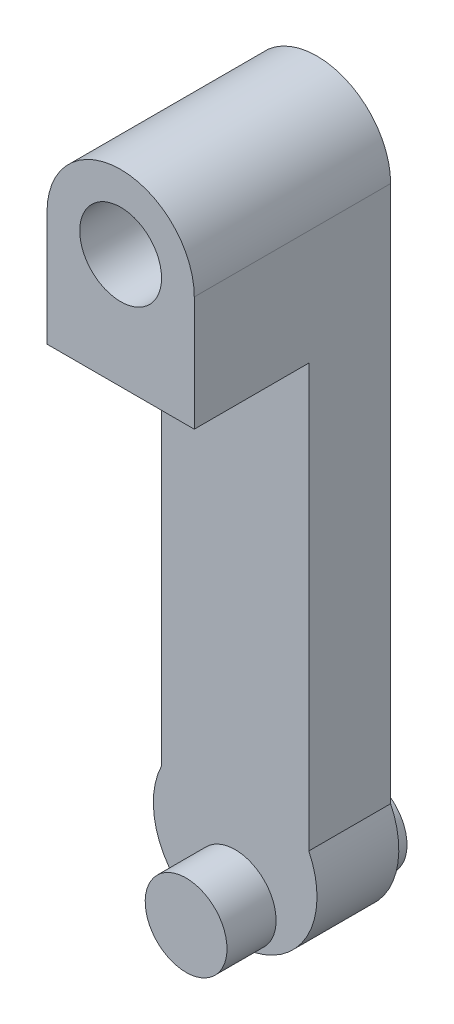
SolidWorks part; units mm, degrees
ref_plane "Front Plane" through (0, 0, 0) normal (0, 0, 1) x (1, 0, 0)
ref_plane "Top Plane" through (0, 0, 0) normal (0, 1, 0) x (1, 0, 0)
ref_plane "Right Plane" through (0, 0, 0) normal (1, 0, 0) x (0, 0, -1)
sketch "Sketch1" plane through (0, 0, 0) normal (0, 0, 1) x (1, 0, 0)
  line L0 (-5.715, 0) -> (-5.715, -41.6821)
  line L1 (5.715, 0) -> (5.715, -41.6821)
  line L2 (-5.715, -44.45) -> (5.715, -44.45) construction
  line L3 (-5.715, -41.6821) -> (-5.715, -44.45) construction
  line L4 (5.715, -41.6821) -> (5.715, -44.45) construction
  circle A0 centre (0, 0) radius 3.175
  arc A1 (5.715, 0) -> (-5.715, 0) centre (0, 0) ccw
  arc A2 (-5.715, -41.6821) -> (5.715, -41.6821) centre (0, -44.45) ccw
  arc A3 (5.715, -41.6821) -> (-5.715, -41.6821) centre (0, -44.45) ccw construction
  dimension "D1" = 6.35
  dimension "D4" = 12.7
  dimension "D2" = 11.43
  dimension "D3" = 44.45
extrude "Boss-Extrude1" add sketch "Sketch1" along normal blind 6.35
sketch "Sketch2" plane through (0, 0, 6.35) normal (0, 0, 1) x (1, 0, 0)
  circle A0 centre (0, -47.625) radius 3.175
  dimension "D1" = 6.35
  dimension "1.85" = 47.625
extrude "Boss-Extrude2" add sketch "Sketch2" along normal blind 3.81
extrude "Boss-Extrude3" add sketch "Sketch2<2>" against normal blind 3.81 from surface starting at face at (0, -21.6918, 0)
sketch "Sketch2<2>" plane through (0, 0, 6.35) normal (0, 0, 1) x (1, 0, 0) same geometry as "Sketch2"
sketch "Sketch4" plane through (0, 0, 6.35) normal (0, 0, 1) x (1, 0, 0)
  line L108 (-5.715, -8.89) -> (5.715, -8.89)
  line L110 (-5.715, 0) -> (-5.715, -41.6821)
  line L111 (5.715, -41.6821) -> (5.715, 0)
  line L112 (-5.715, 0) -> (-5.715, -8.89)
  line L113 (5.715, -8.89) -> (5.715, 0)
  circle A213 centre (0, 0) radius 3.175
  arc A214 (5.715, 0) -> (-5.715, 0) centre (0, 0) ccw
  arc A215 (5.715, 0) -> (-5.715, 0) centre (0, 0) ccw
  dimension "D3" = 6.35
  dimension "D2" = 8.89
  dimension "D1" = 0
extrude "Boss-Extrude4" add sketch "Sketch4" along normal blind 8.89
